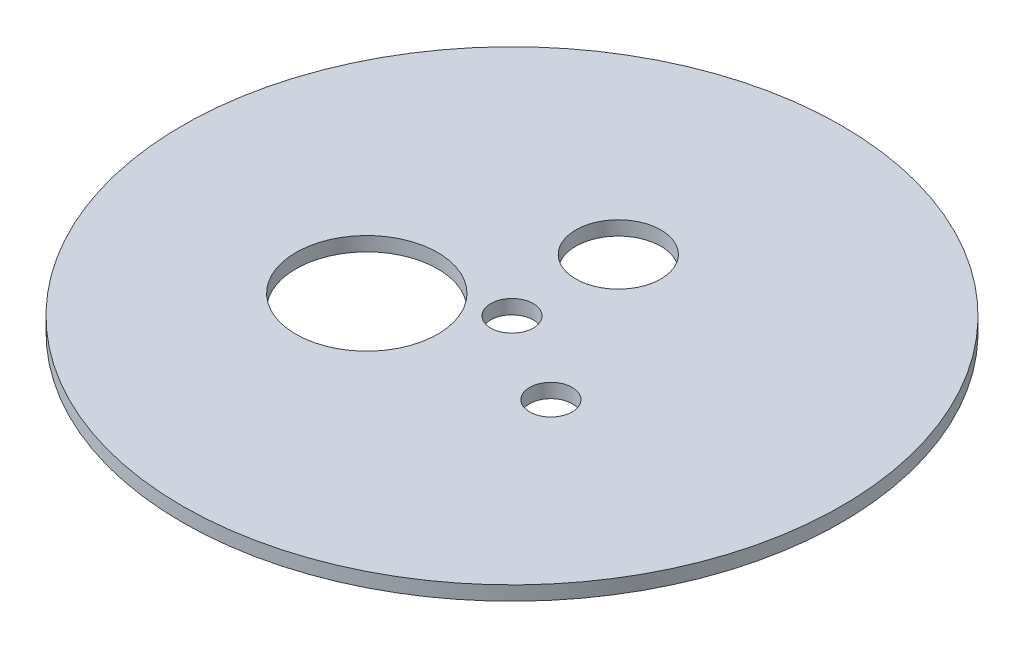
SolidWorks part; units mm, degrees
ref_plane "Front Plane" through (0, 0, 0) normal (0, 0, 1) x (1, 0, 0)
ref_plane "Top Plane" through (0, 0, 0) normal (0, 1, 0) x (1, 0, 0)
ref_plane "Right Plane" through (0, 0, 0) normal (1, 0, 0) x (0, 0, -1)
sketch "Sketch1" plane through (0, 0, 0) normal (0, 1, 0) x (1, 0, 0)
  line L0 (0, 15) -> (0, 0) construction
  line L1 (0, 0) -> (-12.9904, -7.5) construction
  line L2 (0, 0) -> (12.9904, -7.5) construction
  circle A0 centre (0, 0) radius 46.5
  circle A1 centre (0, 15) radius 6
  circle A2 centre (-12.9904, -7.5) radius 10
  circle A3 centre (12.9904, -7.5) radius 3
  circle A4 centre (0, 0) radius 3
  point P3 (0, 15)
  point P8 (12.9904, -7.5)
  point P9 (-12.9904, -7.5)
  point P10 (0, 0)
  dimension "D1" = 93
  dimension "D4" = 12
  dimension "D5" = 20
  dimension "D6" = 6
  dimension "D7" = 6
  dimension "D2" = 15
  dimension "D3" = 3
extrude "Boss-Extrude1" add sketch "Sketch1" along normal blind 2
sketch "Sketch2" plane through (0, 2, 0) normal (0, 1, 0) x (1, 0, 0)
  line L0 (0, 0) -> (12.9904, -7.5) construction
  line L1 (0, 0) -> (0, 46.5) construction
  line L2 (0, 0) -> (-12.9904, -7.5) construction
  line L3 (0, 0) -> (-40.2702, -23.25) construction
  line L4 (0, 0) -> (40.2702, -23.25) construction
  circle A0 centre (0, 0) radius 46.5 construction
  circle A1 centre (-12.9904, -7.5) radius 10 construction
  circle A2 centre (12.9904, -7.5) radius 3 construction
  circle A3 centre (0, 0) radius 25
  circle A4 centre (21.6506, -12.5) radius 3
  circle A5 centre (-21.6506, -12.5) radius 3
  circle A6 centre (0, 25) radius 3
  point P22 (0, 0)
  dimension "D1" = 50
  dimension "D2" = 6
  dimension "D3" = 3
